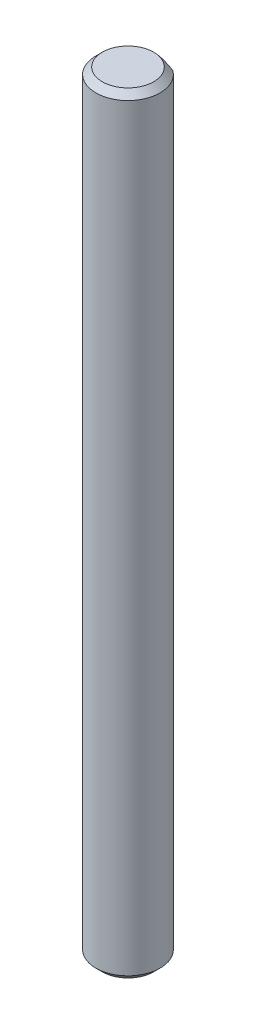
SolidWorks part; units mm, degrees
ref_plane "Спереди" through (0, 0, 0) normal (0, 0, 1) x (1, 0, 0)
ref_plane "Сверху" through (0, 0, 0) normal (0, 1, 0) x (1, 0, 0)
ref_plane "Справа" through (0, 0, 0) normal (1, 0, 0) x (0, 0, -1)
sketch "Эскиз1" plane through (0, 0, 0) normal (0, 1, 0) x (1, 0, 0)
  circle A0 centre (0, 0) radius 2.5
extrude "Бобышка-Вытянуть1" add sketch "Эскиз1" along normal blind 60
sketch "Эскиз2" plane through (0, 60, 0) normal (0, 1, 0) x (1, 0, 0)
  line L0 (0, -2.5) -> (-4.2999, -2.5) construction
  line L1 (-1.5, 2) -> (1.5, 2)
  circle A0 centre (0, 0) radius 2.5 construction
  arc A1 (1.5, 2) -> (-1.5, 2) centre (0, 0) ccw
  dimension "D1" = 4.5
  dimension "D2" = 5
extrude "Вырез-Вытянуть1" cut sketch "Эскиз2" against normal blind 15
chamfer "Фаска1" distance 0.5 angle 45 2 edges at (0, 60, 2.5) (0, 0, 2.5)
